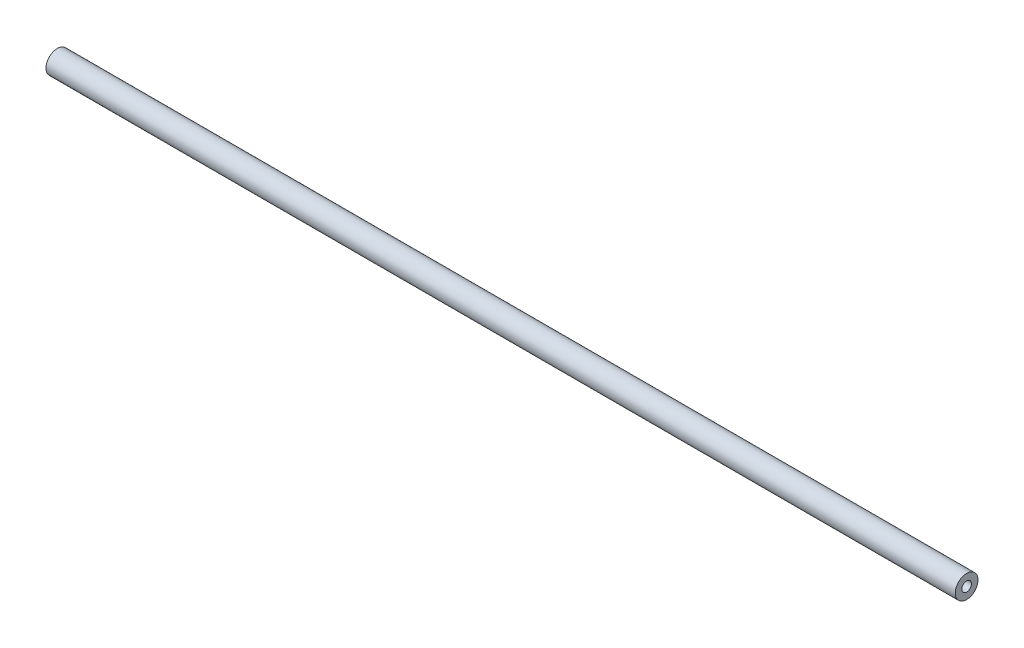
SolidWorks part; units mm, degrees
material "7075-T6 (SN)"
ref_plane "Front Plane" through (0, 0, 0) normal (0, 0, 1) x (1, 0, 0)
ref_plane "Top Plane" through (0, 0, 0) normal (0, 1, 0) x (1, 0, 0)
ref_plane "Right Plane" through (0, 0, 0) normal (1, 0, 0) x (0, 0, -1)
sketch "Sketch1" plane through (0, 0, 0) normal (1, 0, 0) x (0, 0, -1)
  circle A1 centre (0, 0) radius 4.7625
  dimension "D1" = 9.525
extrude "Boss-Extrude1" add sketch "Sketch1" along normal mid plane 381 contours A1 region at (0, 0, 0)
hole_wizard "#10-32 Tapped Hole1" positions "3DSketch1" profile "Sketch2" tap size "#10-32" standard "ANSI Inch"
sketch3d "3DSketch1"
  line L0 (190.5, 0, 0) -> (-190.5, 0, 0) construction
  point P0 (190.5, 0, 0)
  point P7 (-190.5, 0, 0)
sketch "Sketch2" plane through (190.5, 0, 0) normal (0, 1, 0) x (0, 0, -1)
  line L0 (0, 0) -> (0, 13.2428)
  line L1 (0, 13.2428) -> (2.0193, 12.0294)
  line L2 (2.0193, 12.0294) -> (2.0193, 0)
  line L5 (2.0193, 0) -> (0, 0)
  line L10 (0, 13.2428) -> (-2.0193, 12.0294) construction
  line L11 (0, -6.35) -> (0, 107.95) construction
  dimension "Tap Drill Dia." = 4.0386
  dimension "Tap Drill Depth" = 12.0294
  dimension "Drill Angle" = 118
cosmetic thread "Hole Thread1"
cosmetic thread "Hole Thread2"
